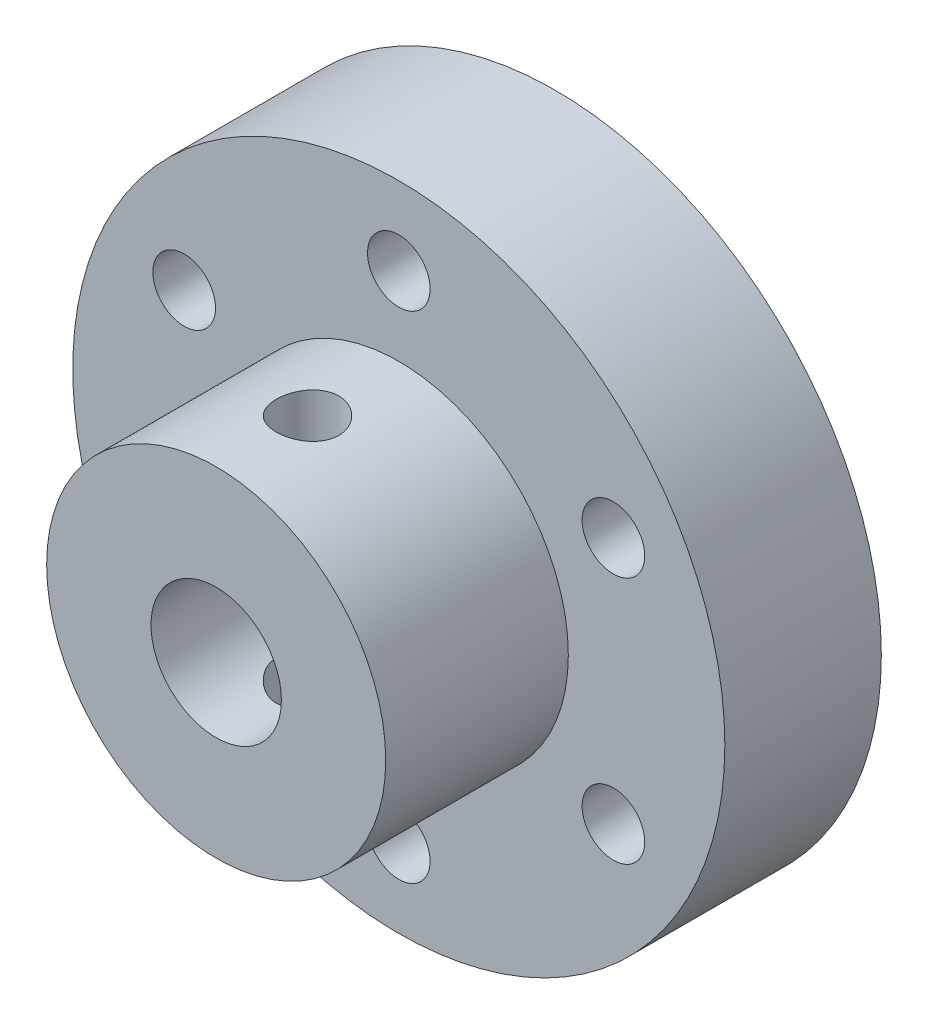
SolidWorks part; units mm, degrees
ref_plane "Front Plane" through (0, 0, 0) normal (0, 0, 1) x (1, 0, 0)
ref_plane "Top Plane" through (0, 0, 0) normal (0, 1, 0) x (1, 0, 0)
ref_plane "Right Plane" through (0, 0, 0) normal (1, 0, 0) x (0, 0, -1)
sketch "Sketch2" plane through (0, 0, 0) normal (0, 0, 1) x (1, 0, 0)
  circle A0 centre (0, 0) radius 12.5
  dimension "D1" = 25
extrude "Boss-Extrude1" add sketch "Sketch2" along normal blind 6
sketch "Sketch3" plane through (0, 0, 6) normal (0, 0, 1) x (1, 0, 0)
  circle A0 centre (0, 0) radius 6.5
  circle A1 centre (0, 0) radius 2.5
  dimension "D1" = 5
  dimension "D2" = 4
extrude "Boss-Extrude2" add sketch "Sketch3" along normal blind 7
sketch "Sketch4" plane through (0, 0, 0) normal (0, 1, 0) x (1, 0, 0)
  line L2 (-12.5, -6) -> (12.5, -6) construction
  circle A0 centre (0, -9.5) radius 1.2
  dimension "D1" = 2.4
  dimension "D2" = 3.5
extrude "Cut-Extrude1" cut sketch "Sketch4" against normal blind 25 and the other way blind 25
sketch "Sketch5" plane through (0, 0, 6) normal (0, 0, 1) x (1, 0, 0)
  circle A0 centre (0, 9.5) radius 1.2
  circle A1 centre (0, 0) radius 12.5 construction
  dimension "D1" = 2.4
  dimension "D2" = 9.5
extrude "Cut-Extrude2" cut sketch "Sketch5" against normal blind 25 and the other way blind 25
ref_axis "Axis1" through (0, 0, -0.6) along (0, 0, 1)
pattern_circular "CirPattern1" count 6 over 360 about axis through (0, 0, -0.6) along (0, 0, 1) of "Cut-Extrude2"
